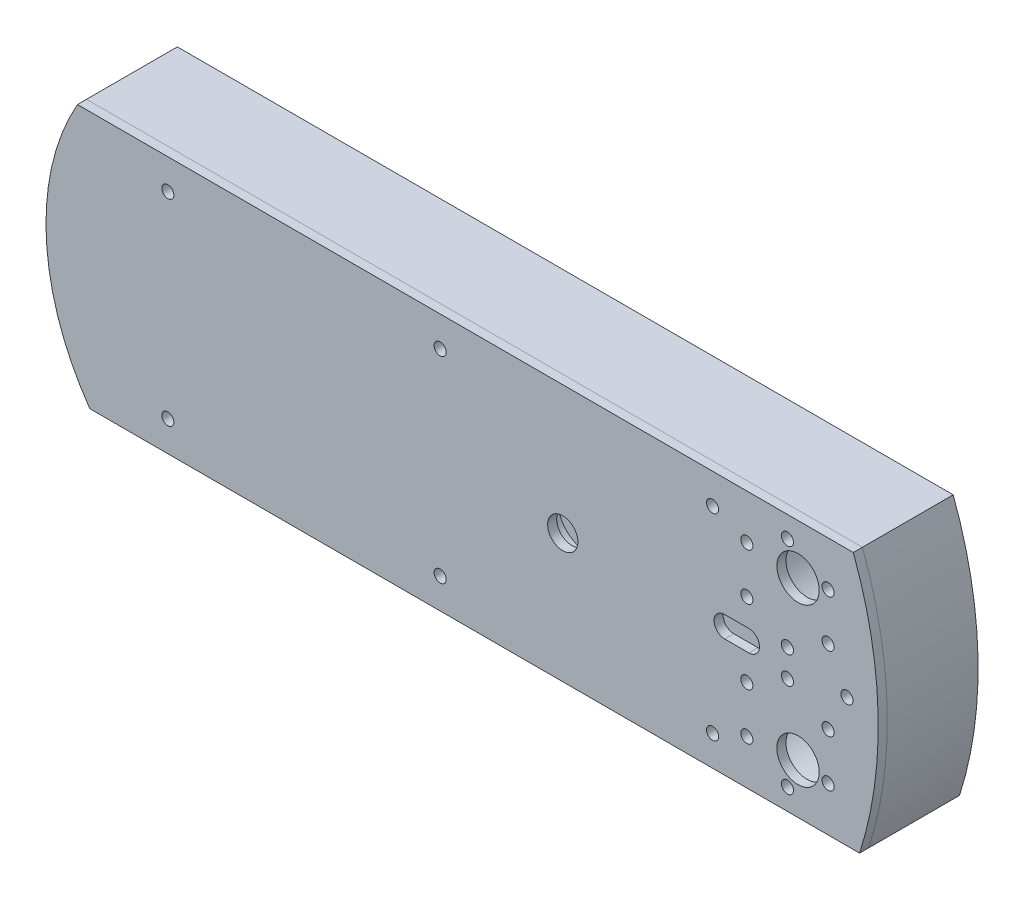
SolidWorks part; units mm, degrees
ref_plane "Front Plane" through (0, 0, 0) normal (0, 0, 1) x (1, 0, 0)
ref_plane "Top Plane" through (0, 0, 0) normal (0, 1, 0) x (1, 0, 0)
ref_plane "Right Plane" through (0, 0, 0) normal (1, 0, 0) x (0, 0, -1)
sketch "Sketch2" plane through (0, 0, 0) normal (0, 0, 1) x (1, 0, 0)
  line L0 (-99.6042, 42.5) -> (156.7694, 42.5)
  line L1 (158.8436, -42.5) -> (-95.5176, -42.5)
  line L3 (31.0775, -42.5) -> (158.8436, -42.5) construction
  arc A0 (-99.6042, 42.5) -> (-95.5176, -42.5) centre (-30.5922, 3.2198) ccw
  arc A2 (158.8436, -42.5) -> (156.7694, 42.5) centre (35.1589, -2.9929) ccw
  arc A3 (158.8436, -42.5) -> (156.7694, 42.5) centre (35.1589, -2.9929) ccw construction
  circle A4 centre (135, 20) radius 18.5
  circle A5 centre (135, -20) radius 18.5
  circle A6 centre (135, 20) radius 18.5 construction
  circle A7 centre (135, -20) radius 18.5 construction
  arc A9 (-104, 33.5) -> (-109.8846, 7.5) centre (-30.5922, 3.2198) ccw construction
  circle A10 centre (60.7519, 0) radius 9.5
  circle A12 centre (138.5, 26.0622) radius 6 construction
  circle A13 centre (138.5, 26.0622) radius 7.5
  circle A14 centre (138.5, -26.0622) radius 7.5
  circle A16 centre (138.5, -26.0622) radius 6 construction
  circle M24 centre (-55.8, -21.5) radius 2.5
  arc M54 (-109.2731, -7.5) -> (-101, -33.5) centre (-30.5922, 3.2198) ccw
  line M55 (-101, -33.5) -> (103.5, -33.5)
  arc M56 (103.5, -33.5) -> (105.5192, -28.5) centre (35.1589, -2.9929) ccw
  arc M64 (0, -9.8966) -> (-2.3966, -7.5) centre (-2.3966, -9.8966) ccw
  line M65 (-2.3966, -7.5) -> (-109.2731, -7.5)
  line M66 (105.5192, -28.5) -> (2.3966, -28.5)
  arc M67 (2.3966, -28.5) -> (0, -26.1034) centre (2.3966, -26.1034) cw
  line M68 (0, -26.1034) -> (0, -9.8966)
  dimension "D1" = 19
  dimension "D3" = 15
  dimension "D4" = 82
  dimension "D5" = 82
extrude "Boss-Extrude1" add sketch "Sketch2" along normal blind 30 contours L1 L0 A4 A5 A10 M65 M64 M68 M67 M66 M56 M55 | M65 M55 M56 M66 M67 M68 M64 M24 | M65 M54 M55 | L0 A0 M65 | A0 L1 M55 region at (26.7265, 4.2833, 0) region at (-36.1007, -22.0427, 0)
sketch "Sketch3" plane through (0, 0, 30) normal (0, 0, 1) x (1, 0, 0)
  line L0 (20.2519, 32.5) -> (110.2519, 32.5) construction
  line L1 (20.2519, -32.5) -> (110.2519, -32.5) construction
  line L2 (65.2519, 32.5) -> (65.2519, 42.5) construction
  line L3 (-95.5176, -42.5) -> (158.8436, -42.5)
  line L4 (65.2519, -32.5) -> (65.2519, -42.5) construction
  line L5 (-99.6042, 42.5) -> (156.7694, 42.5)
  line L6 (154.6627, 0) -> (133.5503, 21.1124) construction
  line L7 (133.5503, -21.1124) -> (154.6627, 0) construction
  line L8 (154.6627, 0) -> (164.9655, 0) construction
  line L9 (114.2519, 0) -> (122.2519, 0) construction
  line L10 (114.2519, 3.5) -> (122.2519, 3.5)
  line L11 (114.2519, -3.5) -> (122.2519, -3.5)
  line L12 (158.8436, -42.5) -> (-95.5176, -42.5) construction
  line L13 (114.2519, 13.5) -> (122.2519, 13.5) construction
  line L14 (158.8436, -42.5) -> (-95.5176, -42.5) construction
  line L15 (-99.6042, 42.5) -> (156.7694, 42.5) construction
  line L16 (114.2519, -13.5) -> (122.2519, -13.5) construction
  line L17 (20.2519, -32.5) -> (-69.7481, -32.5) construction
  line L18 (20.2519, 32.5) -> (-69.7481, 32.5) construction
  circle A0 centre (-30.5922, 3.2198) radius 79.4078
  circle A1 centre (35.1589, -2.9929) radius 129.8411
  circle A2 centre (148.4234, 27.75) radius 2
  circle A3 centre (148.4234, 12.25) radius 2
  circle A4 centre (138.5, -26.0622) radius 7
  circle A5 centre (121.5766, -27.75) radius 2
  circle A6 centre (121.5766, 12.25) radius 2
  circle A7 centre (135, 4.5) radius 2
  circle A8 centre (121.5766, 27.75) radius 2
  circle A9 centre (121.5766, -12.25) radius 2
  circle A10 centre (135, -4.5) radius 2
  circle A11 centre (148.4234, -12.25) radius 2
  circle A12 centre (148.4234, -27.75) radius 2
  circle A13 centre (135, -35.5) radius 2
  circle A14 centre (135, 35.5) radius 2
  circle A15 centre (138.5, 26.0622) radius 7
  circle A16 centre (60.7519, 0) radius 5
  circle A17 centre (-69.7481, 32.5) radius 2
  arc A18 (122.2519, -13.5) -> (122.2519, 13.5) centre (122.2519, 0) ccw construction
  arc A19 (114.2519, 3.5) -> (114.2519, -3.5) centre (114.2519, 0) ccw
  arc A20 (114.2519, 13.5) -> (114.2519, -13.5) centre (114.2519, 0) ccw construction
  circle A21 centre (138.5, -26.0622) radius 6 construction
  circle A22 centre (138.5, 26.0622) radius 6 construction
  circle A23 centre (20.2519, 32.5) radius 2
  circle A24 centre (110.2519, 32.5) radius 2
  circle A25 centre (154.6627, 0) radius 2
  circle A26 centre (20.2519, -32.5) radius 2
  circle A27 centre (110.2519, -32.5) radius 2
  circle A28 centre (60.7519, 0) radius 40 construction
  circle A30 centre (-69.7481, -32.5) radius 2
  arc A31 (158.8436, -42.5) -> (156.7694, 42.5) centre (35.1589, -2.9929) ccw construction
  arc A32 (122.2519, -3.5) -> (122.2519, 3.5) centre (122.2519, 0) ccw
  circle A35 centre (60.7519, 0) radius 9.5 construction
  arc A36 (-104, 33.5) -> (-101, -33.5) centre (-30.5922, 3.2198) ccw construction
  point P79 (65.2519, -32.5)
  point P86 (65.2519, 32.5)
  point P92 (118.2519, 0)
  line M3 (-95.5176, -42.5) -> (158.8436, -42.5)
  circle M7 centre (60.7519, 0) radius 9.5
  circle M73 centre (135, -20) radius 18.5
  circle M78 centre (135, 20) radius 18.5
  line M79 (156.7694, 42.5) -> (-99.6042, 42.5)
  arc M93 (-99.6042, 42.5) -> (-95.5176, -42.5) centre (-30.5922, 3.2198) ccw
  circle M99 centre (-55.8, -21.5) radius 2.5
  arc M113 (158.8436, -42.5) -> (156.7694, 42.5) centre (35.1589, -2.9929) ccw
  dimension "D1" = 4
  dimension "D2" = 14
  dimension "D3" = 4
  dimension "D7" = 10
  dimension "D8" = 3.5
  dimension "D6" = 4.5
  dimension "D4" = 10
  dimension "D5" = 90
  dimension "D10" = 8
  dimension "D11" = 10
extrude "Boss-Extrude2" add sketch "Sketch3" along normal blind 3 separate body contours A1 M79 M93 M3 | L5 A1 L3 A0 A30 A26 A23 A17 M99 | A0 L3 A32 L11 A19 L10 A27 A25 A24 M113 M79 M7 M78 M73 | A15 A14 A8 A7 A6 A3 A2 M78 | A13 A12 A11 A10 A9 A5 A4 M73 | A16 M7 | M99 region at (-99.4704, 3.0231, 30) region at (-23.6679, 0.1288, 30) region at (95.9333, -0.4712, 30) region at (51.5206, 0, 30) region at (134.363, -18.8968, 30) region at (134.363, 18.8968, 30) region at (-55.8, -21.5, 30)
sketch "Sketch6" plane through (0, 0, 0) normal (0, 0, -1) x (-1, 0, 0)
  circle A0 centre (-60.7519, 0) radius 5.5
  circle A1 centre (-60.7519, 0) radius 9.5
  circle A3 centre (-60.7519, 0) radius 9.5 construction
  dimension "D1" = 11
extrude "Boss-Extrude3" add sketch "Sketch6" against normal offset from surface (20 mm away) 5 from offset 5 up to face at (28.8246, -0.1048, 30) offset against normal yes
